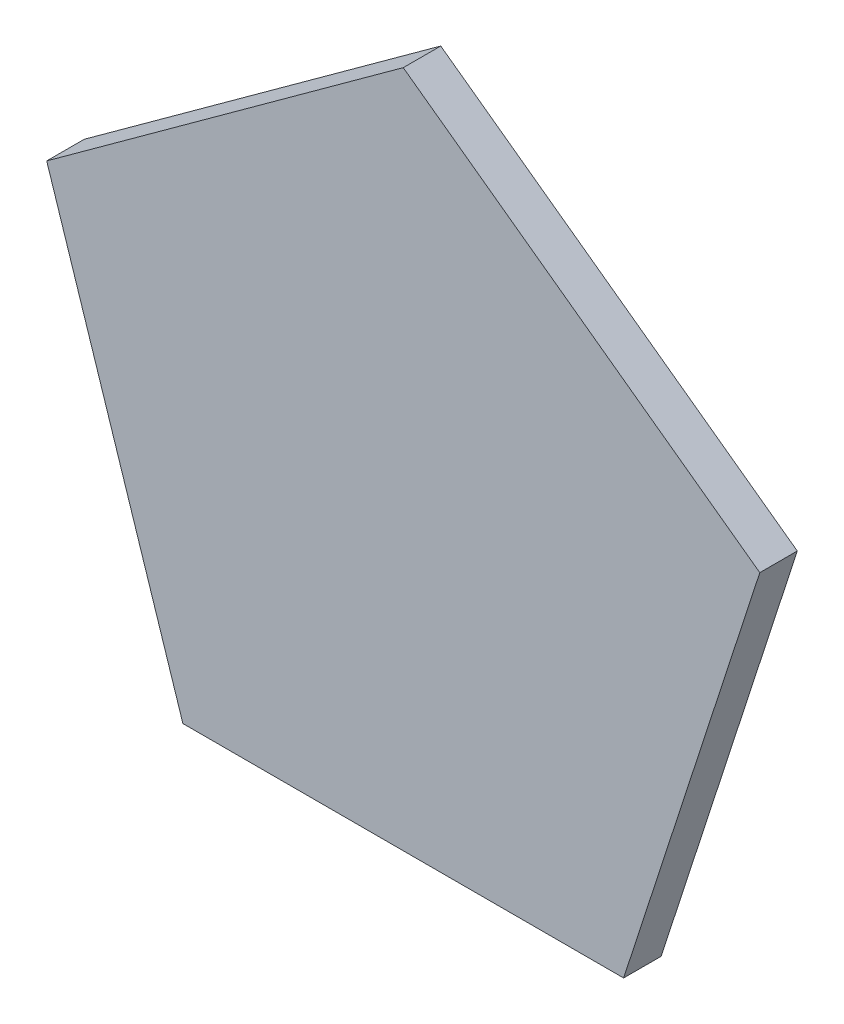
SolidWorks part; units mm, degrees
ref_plane "Alzado" through (0, 0, 0) normal (0, 0, 1) x (1, 0, 0)
ref_plane "Planta" through (0, 0, 0) normal (0, 1, 0) x (1, 0, 0)
ref_plane "Vista lateral" through (0, 0, 0) normal (1, 0, 0) x (0, 0, -1)
sketch "Croquis1" plane through (0, 0, 0) normal (0, 0, 1) x (1, 0, 0)
  line L0 (0, 10) -> (-9.5106, 3.0902)
  line L1 (-9.5106, 3.0902) -> (-5.8779, -8.0902)
  line L2 (-5.8779, -8.0902) -> (5.8779, -8.0902)
  line L3 (5.8779, -8.0902) -> (9.5106, 3.0902)
  line L4 (9.5106, 3.0902) -> (0, 10)
  line L5 (0, 9.5056) -> (-9.0403, 2.9374)
  line L6 (-9.0403, 2.9374) -> (-5.5872, -7.6902)
  line L7 (-5.5872, -7.6902) -> (5.5872, -7.6902)
  line L8 (5.5872, -7.6902) -> (9.0403, 2.9374)
  line L9 (9.0403, 2.9374) -> (0, 9.5056)
  line L10 (-0.0173, -3.9) -> (5.3151, -7.6902)
  line L11 (5.6639, -7.4542) -> (3.5687, -1.2268)
  line L12 (3.5687, -1.2268) -> (8.96, 2.6902)
  line L13 (8.83, 3.0902) -> (2.24, 3.0902)
  line L14 (2.24, 3.0902) -> (0.2097, 9.3532)
  line L15 (-0.2109, 9.3523) -> (-2.2503, 3.0902)
  line L16 (-2.2503, 3.0902) -> (-8.83, 3.0902)
  line L17 (-8.96, 2.6902) -> (-3.5858, -1.2144)
  line L18 (-3.5858, -1.2144) -> (-5.6649, -7.4512)
  line L19 (-0.0173, -3.9) -> (-5.3184, -7.6902)
  circle A0 centre (0, 0) radius 10 construction
  dimension "D1" = 20
  dimension "D2" = 108
  dimension "D3" = 108
  dimension "108" = 108
  dimension "D4" = 0.4
  dimension "D5" = 0.4
  dimension "D6" = 0.4
  dimension "D7" = 0.4
  dimension "D8" = 0.4
  dimension "D9" = 3.9
  dimension "D10" = 36
  dimension "D11" = 36
  dimension "D12" = 36
  dimension "D13" = 36
  dimension "D14" = 36
  dimension "D15" = 2.24
extrude "Saliente-Extruir1" add sketch "Croquis1" against normal blind 1 contours L3 L4 L0 L1 L2 L9 L8 L7 L6 L5 | L19 L10 L7 L8 L11 L12 L9 L13 L14 L5 L15 L16 L6 L17 L18 region at (4.601, 6.3327, 0) region at (-0.002, -0.0074, 0)
extrude "Saliente-Extruir2" add sketch "Croquis1<3>" against normal blind 0.5 contours L14 L13 L9 | L16 L15 L5 | L18 L17 L6 | L10 L19 L7 | L12 L11 L8 region at (-3.7637, 5.1776, 0) region at (3.7599, 5.1779, 0) region at (-6.0702, -1.9918, 0) region at (6.0642, -1.997, 0) region at (-0.0069, -6.4268, 0)
sketch "Croquis1<3>" plane through (0, 0, 0) normal (0, 0, 1) x (1, 0, 0) same geometry as "Croquis1"
